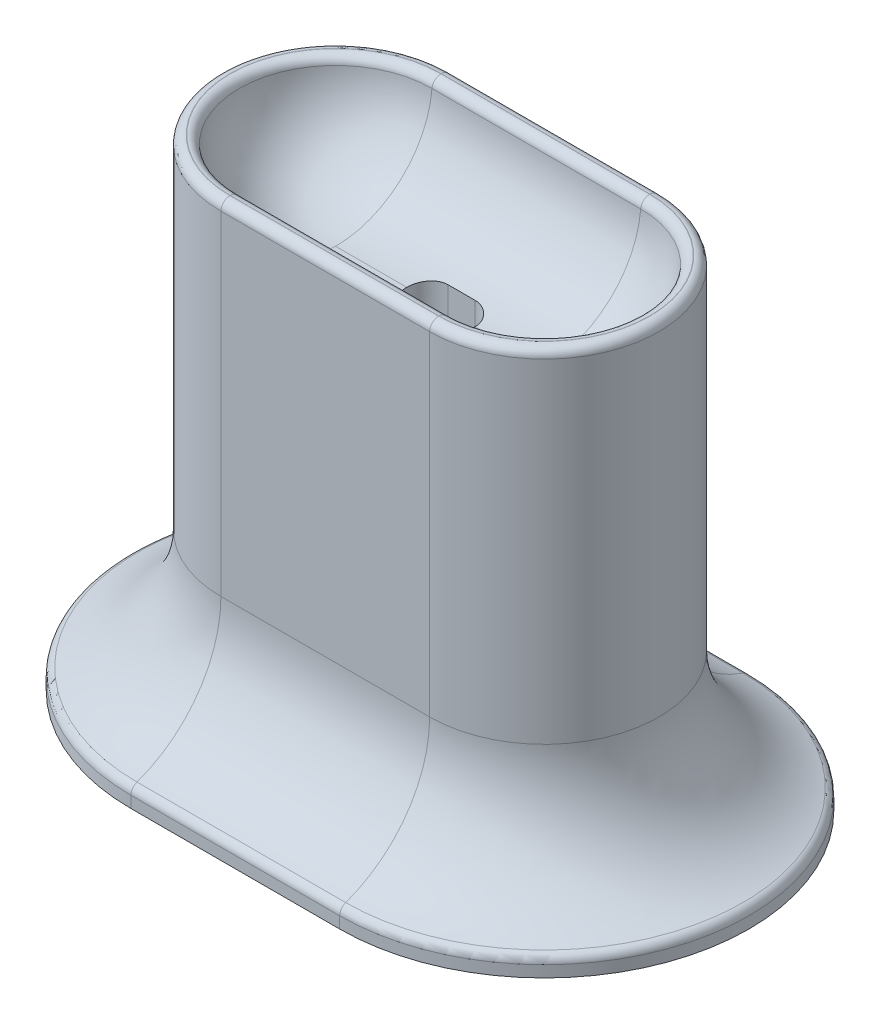
SolidWorks part; units mm, degrees
ref_plane "Front Plane" through (0, 0, 0) normal (0, 0, 1) x (1, 0, 0)
ref_plane "Top Plane" through (0, 0, 0) normal (0, 1, 0) x (1, 0, 0)
ref_plane "Right Plane" through (0, 0, 0) normal (1, 0, 0) x (0, 0, -1)
sketch "Sketch2" plane through (0, 0, 0) normal (0, 1, 0) x (1, 0, 0)
  line L0 (0, 10.75) -> (23.2, 10.75)
  line L1 (0, -10.75) -> (23.2, -10.75)
  line L2 (0, -12.75) -> (23.2, -12.75)
  line L3 (0, 12.75) -> (23.2, 12.75)
  line L4 (0, 22.75) -> (23.2, 22.75)
  line L5 (0, -22.75) -> (23.2, -22.75)
  arc A0 (0, 10.75) -> (0, -10.75) centre (0, 0) ccw
  arc A1 (23.2, -10.75) -> (23.2, 10.75) centre (23.2, 0) ccw
  arc A2 (0, 12.75) -> (0, -12.75) centre (0, 0) ccw
  arc A3 (23.2, -12.75) -> (23.2, 12.75) centre (23.2, 0) ccw
  arc A4 (23.2, -22.75) -> (23.2, 22.75) centre (23.2, 0) ccw
  arc A5 (0, 22.75) -> (0, -22.75) centre (0, 0) ccw
  dimension "D1" = 21.5
  dimension "D2" = 23.2
  dimension "D3" = 2
  dimension "D4" = 10
extrude "Boss-Extrude1" add sketch "Sketch2" along normal blind 53.5 contours L2 A3 L3 A2 A1 L1 A0 L0 region at (-12.2003, 0, 0)
extrude "Boss-Extrude2" add sketch "Sketch2<3>" against normal blind 10 from offset 42.75 contours L1 A1 L0 A0 region at (11.6, 0, 0)
sketch "Sketch2<3>" plane through (0, 0, 0) normal (0, 1, 0) x (1, 0, 0) same geometry as "Sketch2"
extrude "Boss-Extrude3" add sketch "Sketch2<4>" along normal blind 2 contours L4 A5 L5 A4 A3 L2 A2 L3 region at (11.6, 0, -21.926)
sketch "Sketch2<4>" plane through (0, 0, 0) normal (0, 1, 0) x (1, 0, 0) same geometry as "Sketch2"
fillet "Fillet1" radius 10.75 4 edges at (11.6, 42.75, -10.75) (33.95, 42.75, 0) (11.6, 42.75, 10.75) (-10.75, 42.75, 0)
fillet "Fillet2" radius 14 4 edges at (-12.75, 2, 0) (11.6, 2, -12.75) (35.95, 2, 0) (11.6, 2, 12.75)
fillet "Fillet3" radius 1 12 edges at (-22.75, 2, 0) (11.6, 2, 22.75) (45.95, 2, 0) (-10.75, 53.5, 0) (11.6, 53.5, 10.75) (33.95, 53.5, 0) (-12.75, 53.5, 0) (11.6, 53.5, 12.75) (35.95, 53.5, 0) (11.6, 2, -22.75) (11.6, 53.5, -10.75) (11.6, 53.5, -12.75)
sketch "Sketch3" plane through (0, 32.75, 0) normal (0, -1, 0) x (1, 0, 0)
  line L0 (10.2, 2.3) -> (13.2, 2.3)
  line L1 (10.2, -2.3) -> (13.2, -2.3)
  arc A0 (10.2, 2.3) -> (10.2, -2.3) centre (10.2, 0) ccw
  arc A1 (13.2, -2.3) -> (13.2, 2.3) centre (13.2, 0) ccw
  arc A2 (23.2, -10.75) -> (23.2, 10.75) centre (23.2, 0) ccw construction
  point P1 (15.5, 0)
  point P10 (33.95, 0)
  dimension "D1" = 4.6
  dimension "D2" = 3
  dimension "D3" = 18.45
extrude "Cut-Extrude1" cut sketch "Sketch3" against normal through all both and the other way through all
sketch "Sketch4" plane through (0, 0, -10.75) normal (0, 0, 1) x (1, 0, 0)
  line L0 (0, 2.2171) -> (23.2, 2.2171) construction
  line L3 (10.6, 1.099) -> (10.6, 0)
  line L4 (12.6, 1.099) -> (12.6, 0)
  line L7 (10.6, 0) -> (12.6, 0)
  arc A0 (12.6, 1.099) -> (10.6, 1.099) centre (11.6, 2.2171) ccw
  dimension "D1" = 3
extrude "Cut-Extrude2" cut sketch "Sketch4" against normal through all
fillet "Fillet4" radius 0.5 5 edges at (12.6869, 1.1833, -22.75) (13.0478, 1.8246, -22.5849) (10.5131, 1.1833, -22.75) (10.1531, 1.8214, -22.5871) (11.6985, 3.7138, -19.0656)
